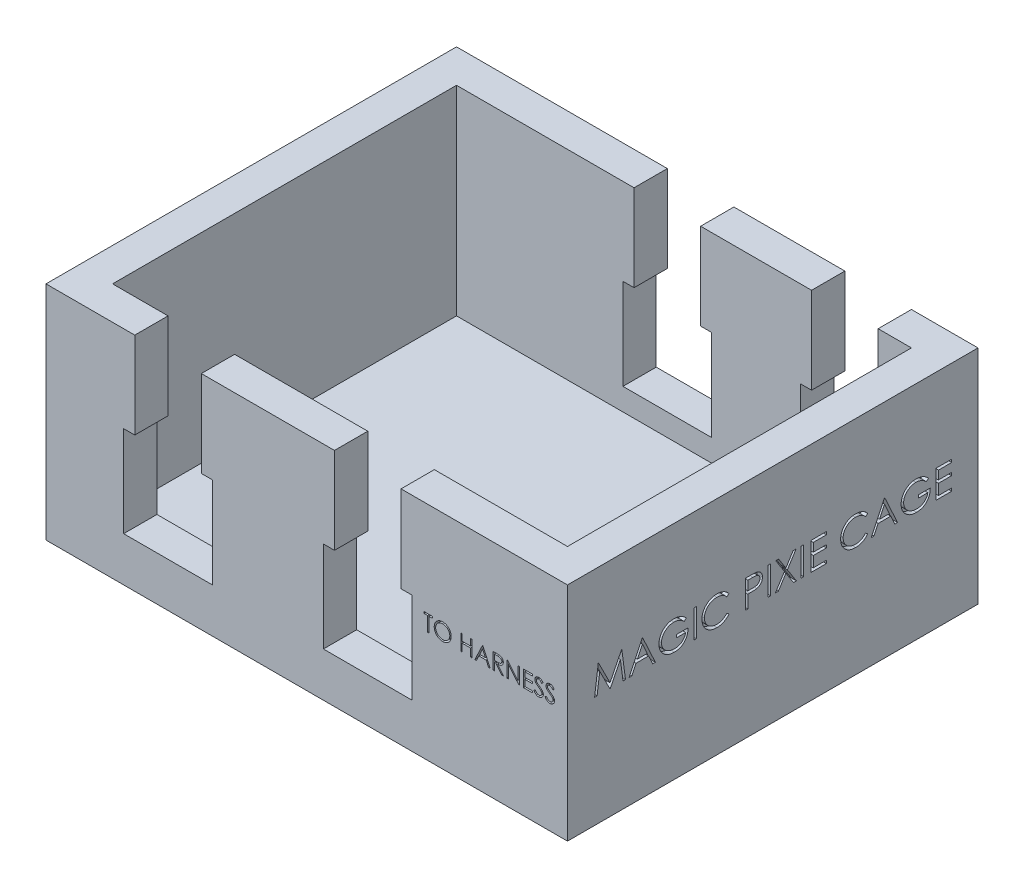
SolidWorks part; units mm, degrees
ref_plane "Front Plane" through (0, 0, 0) normal (0, 0, 1) x (1, 0, 0)
ref_plane "Top Plane" through (0, 0, 0) normal (0, 1, 0) x (1, 0, 0)
ref_plane "Right Plane" through (0, 0, 0) normal (1, 0, 0) x (0, 0, -1)
sketch "Sketch2" plane through (0, 0, 0) normal (0, 1, 0) x (1, 0, 0)
  line L0 (-29.845, -23.495) -> (-29.845, 23.495)
  line L1 (-26.035, -19.685) -> (26.035, -19.685)
  line L2 (-26.035, -19.685) -> (-26.035, 19.685)
  line L3 (-26.035, 19.685) -> (26.035, 19.685)
  line L4 (26.035, -19.685) -> (26.035, 19.685)
  line L5 (-26.035, -19.685) -> (26.035, 19.685) construction
  line L6 (-26.035, 19.685) -> (26.035, -19.685) construction
  line L7 (-29.845, 23.495) -> (29.845, 23.495)
  line L8 (29.845, -23.495) -> (29.845, 23.495)
  line L9 (-29.845, -23.495) -> (29.845, -23.495)
  point P0 (0, 0)
  dimension "D1" = 52.07
  dimension "D2" = 39.37
  dimension "D3" = 3.81
extrude "Boss-Extrude1" add sketch "Sketch2" along normal blind 2.54 contours L1 L4 L3 L2 | L0 L9 L8 L7 L4 L1 L2 L3 | L2 L1 L4 L3 | L0 L7 L8 L9 region at (-29.0853, 0, 0) region at (0, 0, 0)
extrude "Boss-Extrude2" add sketch "Sketch2<3>" along normal blind 25.4
sketch "Sketch2<3>" plane through (0, 0, 0) normal (0, 1, 0) x (1, 0, 0) same geometry as "Sketch2"
sketch "Sketch3" plane through (0, 0, 23.495) normal (0, 0, 1) x (1, 0, 0)
  line L0 (-29.845, 25.4) -> (-29.845, 0) construction
  line L1 (-10.795, 5.08) -> (-20.955, 5.08)
  line L2 (-10.795, 5.08) -> (-10.795, 15.494)
  line L3 (-10.795, 15.494) -> (-20.955, 15.494)
  line L4 (-20.955, 5.08) -> (-20.955, 15.494)
  line L5 (-10.795, 5.08) -> (-20.955, 15.494) construction
  line L6 (-10.795, 15.494) -> (-20.955, 5.08) construction
  line L7 (12.065, 5.08) -> (1.905, 5.08)
  line L8 (12.065, 5.08) -> (12.065, 15.494)
  line L9 (12.065, 15.494) -> (1.905, 15.494)
  line L10 (1.905, 5.08) -> (1.905, 15.494)
  line L11 (12.065, 5.08) -> (1.905, 15.494) construction
  line L12 (12.065, 15.494) -> (1.905, 5.08) construction
  line L13 (-29.845, 0) -> (29.845, 0) construction
  line L14 (-29.845, 25.4) -> (29.845, 25.4) construction
  line L15 (-19.685, 25.4) -> (-12.065, 25.4)
  line L16 (-19.685, 25.4) -> (-19.685, 15.494)
  line L17 (-19.685, 15.494) -> (-12.065, 15.494)
  line L18 (-12.065, 25.4) -> (-12.065, 15.494)
  line L20 (3.175, 25.4) -> (10.795, 25.4)
  line L21 (3.175, 25.4) -> (3.175, 15.494)
  line L22 (3.175, 15.494) -> (10.795, 15.494)
  line L23 (10.795, 25.4) -> (10.795, 15.494)
  point P0 (-15.875, 10.287)
  point P5 (6.985, 10.287)
  point P24 (6.985, 15.494)
  point P25 (6.985, 25.4)
  point P26 (-15.875, 25.4)
  point P27 (-15.875, 15.494)
  line M16 (29.845, 25.4) -> (-29.845, 25.4)
  dimension "D1" = 8.89
  dimension "D2" = 5.08
  dimension "D3" = 10.16
  dimension "D4" = 10.414
  dimension "D5" = 12.7
  dimension "D6" = 10.16
  dimension "D7" = 10.414
  dimension "D8" = 7.62
  dimension "D9" = 7.62
extrude "Cut-Extrude1" cut sketch "Sketch3" against normal blind 25.4 contours L18 L16 L3 M16 | L4 L1 L2 L3 | L23 L21 L9 M16 | L10 L7 L8 L9 region at (6.985, 20.447, 23.495) region at (-15.875, 10.287, 23.495) region at (-15.875, 20.447, 23.495) region at (6.985, 10.287, 23.495)
sketch "Sketch4" plane through (0, 0, -23.495) normal (0, 0, -1) x (-1, 0, 0)
  line L0 (29.845, 0) -> (-29.845, 0) construction
  line L1 (-23.495, 5.08) -> (-13.335, 5.08)
  line L2 (-23.495, 5.08) -> (-23.495, 15.494)
  line L3 (-23.495, 15.494) -> (-13.335, 15.494)
  line L4 (-13.335, 5.08) -> (-13.335, 15.494)
  line L5 (-23.495, 5.08) -> (-13.335, 15.494) construction
  line L6 (-23.495, 15.494) -> (-13.335, 5.08) construction
  line L7 (-3.175, 5.08) -> (6.985, 5.08)
  line L8 (-3.175, 5.08) -> (-3.175, 15.494)
  line L9 (-3.175, 15.494) -> (6.985, 15.494)
  line L10 (6.985, 5.08) -> (6.985, 15.494)
  line L11 (-3.175, 5.08) -> (6.985, 15.494) construction
  line L12 (-3.175, 15.494) -> (6.985, 5.08) construction
  line L13 (-29.845, 25.4) -> (-29.845, 0) construction
  line L14 (-29.845, 25.4) -> (29.845, 25.4) construction
  line L15 (-22.225, 25.4) -> (-14.605, 25.4)
  line L16 (-22.225, 25.4) -> (-22.225, 15.494)
  line L17 (-22.225, 15.494) -> (-14.605, 15.494)
  line L18 (-14.605, 25.4) -> (-14.605, 15.494)
  line L20 (-1.905, 25.4) -> (5.715, 25.4)
  line L21 (-1.905, 25.4) -> (-1.905, 15.494)
  line L22 (-1.905, 15.494) -> (5.715, 15.494)
  line L23 (5.715, 25.4) -> (5.715, 15.494)
  point P0 (-18.415, 10.287)
  point P5 (1.905, 10.287)
  point P24 (-18.415, 25.4)
  point P25 (-18.415, 15.494)
  point P26 (1.905, 25.4)
  point P27 (1.905, 15.494)
  line M19 (29.845, 25.4) -> (-29.845, 25.4)
  dimension "D1" = 10.414
  dimension "D2" = 10.16
  dimension "D3" = 5.08
  dimension "D4" = 6.35
  dimension "D5" = 10.16
  dimension "D6" = 10.16
  dimension "D7" = 10.414
  dimension "D8" = 7.62
  dimension "D9" = 7.62
extrude "Cut-Extrude2" cut sketch "Sketch4" against normal blind 25.4 contours L1 L4 L3 L2 | L18 L16 L3 M19 | L23 L21 L9 M19 | L7 L10 L9 L8 region at (18.415, 10.287, -23.495) region at (-1.905, 20.447, -23.495) region at (18.415, 20.447, -23.495) region at (-1.905, 10.287, -23.495)
sketch "Sketch5" plane through (0, 0, -23.495) normal (0, 0, -1) x (-1, 0, 0)
  line L0 (29.845, 12.7) -> (6.985, 12.7) construction
  line L1 (29.845, 25.4) -> (29.845, 0) construction
  line L2 (6.985, 5.08) -> (6.985, 15.494) construction
  text T0 "TO IGNITERS" font "Century Gothic" height in points 10
extrude "Cut-Extrude3" cut sketch "Sketch5" against normal blind 0.635
sketch "Sketch6" plane through (0, 0, 23.495) normal (0, 0, 1) x (1, 0, 0)
  line L0 (29.845, 12.7) -> (12.065, 12.7) construction
  line L1 (29.845, 25.4) -> (29.845, 0) construction
  line L2 (12.065, 5.08) -> (12.065, 15.494) construction
  text T0 "TO HARNESS" font "Century Gothic" height in points 7
extrude "Cut-Extrude4" cut sketch "Sketch6" against normal blind 0.635
sketch "Sketch7" plane through (-29.845, 0, 0) normal (-1, 0, 0) x (0, 0, 1)
  line L0 (-23.495, 12.6322) -> (23.495, 12.7) construction
  line L1 (23.495, 25.4) -> (23.495, 0) construction
  text T0 "MAGIC PIXIE CAGE"
extrude "Cut-Extrude5" cut sketch "Sketch7" against normal blind 0.635
sketch "Sketch8" plane through (29.845, 0, 0) normal (1, 0, 0) x (0, 0, -1)
  line L0 (-23.495, 12.7) -> (23.495, 12.7) construction
  line L1 (-23.495, 25.4) -> (-23.495, 0) construction
  line L2 (23.495, 25.4) -> (23.495, 0) construction
  text T0 "MAGIC PIXIE CAGE"
extrude "Cut-Extrude6" cut sketch "Sketch8" against normal blind 0.635
